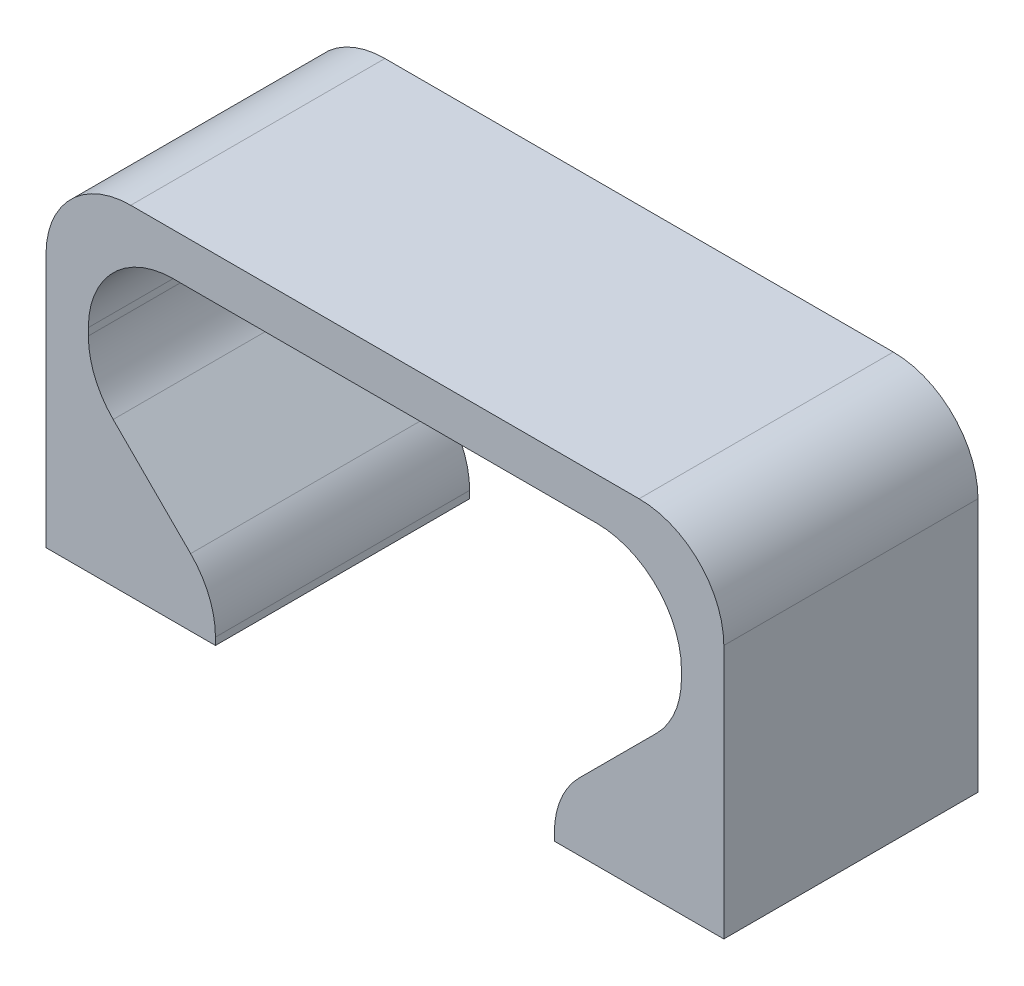
SolidWorks part; units mm, degrees
ref_plane "Front Plane" through (0, 0, 0) normal (0, 0, 1) x (1, 0, 0)
ref_plane "Top Plane" through (0, 0, 0) normal (0, 1, 0) x (1, 0, 0)
ref_plane "Right Plane" through (0, 0, 0) normal (1, 0, 0) x (0, 0, -1)
sketch "Sketch1" plane through (0, 0, 0) normal (0, 0, 1) x (1, 0, 0)
  line L0 (-20, 20) -> (20, 20)
  line L1 (20, 20) -> (20, 0)
  line L2 (20, 0) -> (10, 0)
  line L4 (17.5, 10) -> (17.5, 17.5)
  line L5 (17.5, 17.5) -> (-17.5, 17.5)
  line L6 (-17.5, 17.5) -> (-17.5, 10)
  line L8 (-10, 0) -> (-20, 0)
  line L9 (-20, 0) -> (-20, 20)
  line L10 (-10, 0) -> (10, 0) construction
  line L11 (-20, 10) -> (-17.5, 10) construction
  line L12 (17.5, 10) -> (-17.5, 10) construction
  line L13 (17.5, 10) -> (20, 10) construction
  line L14 (0, 20) -> (0, 17.5) construction
  line L15 (-17.5, 10) -> (-10, 2.5)
  line L16 (-10, 2.5) -> (-10, 0)
  line L17 (10, 0) -> (10, 2.5)
  line L18 (10, 2.5) -> (17.5, 10)
  line L19 (-10, 2.5) -> (10, 2.5) construction
  dimension "D1" = 2.5
  dimension "D2" = 40
  dimension "D3" = 20
  dimension "D4" = 20
  dimension "D5" = 10
  dimension "D6" = 2.5
extrude "Boss-Extrude1" add sketch "Sketch1" along normal blind 7.5 and the other way blind 7.5
fillet "Fillet1" radius 5 8 edges at (20, 20, 0) (-20, 20, 0) (17.5, 17.5, 0) (-17.5, 17.5, 0) (17.5, 10, 0) (10, 2.5, 0) (-10, 2.5, 0) (-17.5, 10, 0)
